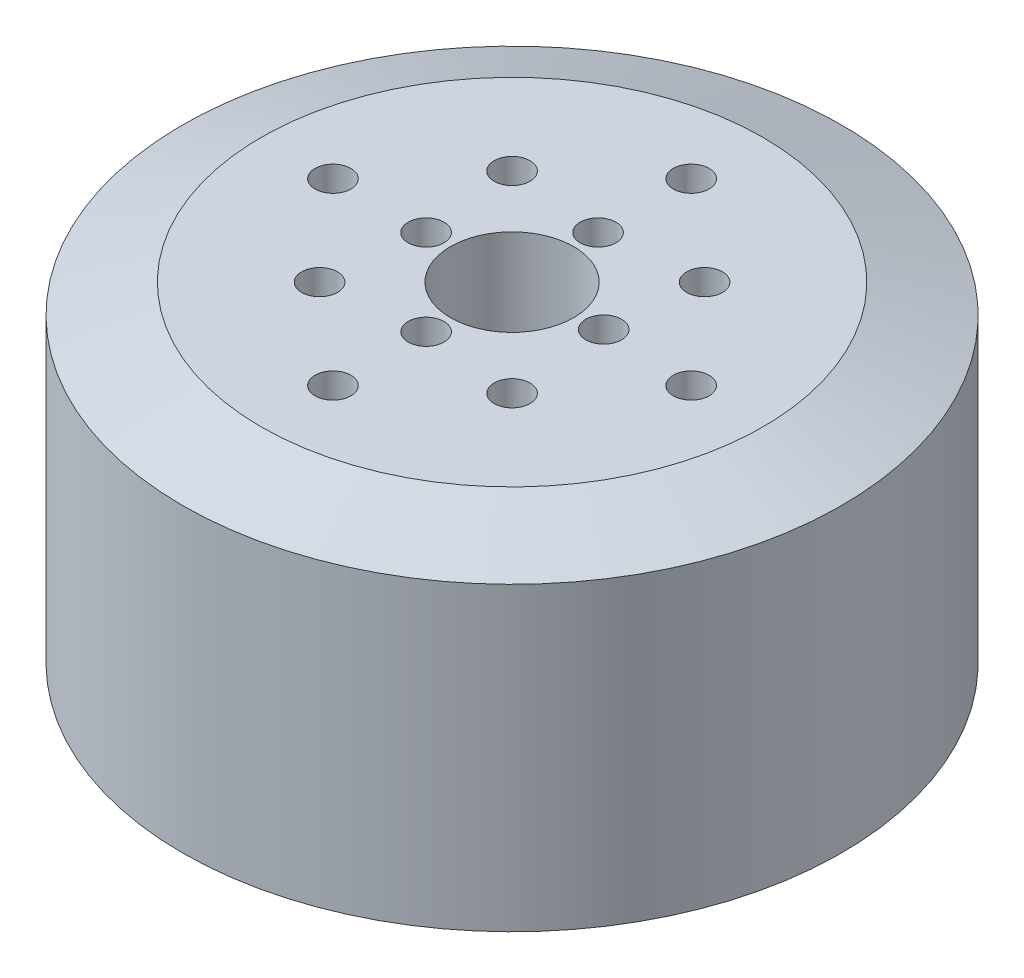
SolidWorks part; units mm, degrees
material "3.1355 (EN-AW 2024)"
ref_plane "Спереди" through (0, 0, 0) normal (0, 0, 1) x (1, 0, 0)
ref_plane "Сверху" through (0, 0, 0) normal (0, 1, 0) x (1, 0, 0)
ref_plane "Справа" through (0, 0, 0) normal (1, 0, 0) x (0, 0, -1)
sketch "Эскиз1" plane through (0, 0, 0) normal (0, 1, 0) x (1, 0, 0)
  circle A0 centre (0, 0) radius 23
  dimension "D1" = 46
extrude "Бобышка-Вытянуть1" add sketch "Эскиз1" along normal blind 23
chamfer "Фаска1" distance 2 angle 70 1 edges at (0, 23, 23) first distance on face at (0, 23, 23)
sketch "Эскиз2" plane through (0, 23, 0) normal (0, 1, 0) x (1, 0, 0)
  circle A0 centre (0, 0) radius 3.5
  circle A1 centre (0, 0) radius 5
  dimension "D1" = 7
  dimension "D2" = 10
extrude "Вырез-Вытянуть1" cut sketch "Эскиз2" against normal through all contours A0 region at (0, 23, 0)
extrude "Бобышка-Вытянуть2" add sketch "Эскиз2<3>" against normal blind 32
sketch "Эскиз2<3>" plane through (0, 23, 0) normal (0, 1, 0) x (1, 0, 0) same geometry as "Эскиз2"
sketch "Эскиз3" plane through (0, 23, 0) normal (0, 1, 0) x (1, 0, 0)
  line L0 (9.5, 0) -> (0, 0) construction
  line L1 (0, 0) -> (6.7175, 6.7175) construction
  line L2 (0, 0) -> (6.7175, -6.7175) construction
  line L3 (0, 0) -> (-6.7175, -6.7175) construction
  line L4 (0, 0) -> (-6.7175, 6.7175) construction
  circle A0 centre (0, 0) radius 6 construction
  circle A1 centre (0, 0) radius 12.5 construction
  circle A2 centre (0, 0) radius 9.5 construction
  point P4 (0, 12.5)
  point P5 (0, -12.5)
  point P6 (-12.5, 0)
  point P7 (12.5, 0)
  point P8 (6, 0)
  point P9 (0, 6)
  point P10 (-6, 0)
  point P11 (0, -6)
  point P21 (0, 0)
  dimension "D1" = 12
  dimension "D2" = 25
  dimension "D3" = 19
  dimension "D4" = 45
  dimension "D5" = 4
sketch "Эскиз4" plane through (0, 0, 0) normal (0, -1, 0) x (1, 0, 0)
  circle A1 centre (0, 0) radius 5 construction
  circle A2 centre (0, 0) radius 21
  circle A3 centre (0, 0) radius 21
  circle A4 centre (0, 0) radius 5
  dimension "D1" = 2
extrude "Вырез-Вытянуть2" cut sketch "Эскиз4" against normal blind 19
hole_wizard "Отверстие обработанное метчиком M3x0.51" positions "Эскиз6" profile "Эскиз5" tap size "M3x0.5" standard "Ansi Metric" end condition through all
sketch "Эскиз6" plane through (0, 23, 0) normal (0, 1, 0) x (1, 0, 0)
  point P0 (0, 12.5)
  point P3 (12.5, 0)
  point P6 (0, -12.5)
  point P9 (-12.5, 0)
sketch "Эскиз5" plane through (0, 23, -12.5) normal (1, 0, 0) x (0, 0, 1)
  line L0 (0, 0) -> (0, 32)
  line L1 (0, 32) -> (1.25, 32)
  line L2 (1.25, 32) -> (1.25, 0)
  line L5 (1.25, 0) -> (0, 0)
  line L11 (0, -6.35) -> (0, 107.95) construction
  dimension "Диаметр проходного сверла" = 2.5
  dimension "Глубина проходного сверла" = 32
cosmetic thread "Отверстие резьбы1" parameters "D2"=3
cosmetic thread "Отверстие резьбы2" parameters "D2"=3
cosmetic thread "Отверстие резьбы3" parameters "D2"=3
cosmetic thread "Отверстие резьбы4" parameters "D2"=3
hole_wizard "Отверстие обработанное метчиком M3x0.52" positions "Эскиз8" profile "Эскиз7" tap size "M3x0.5" standard "Ansi Metric"
sketch "Эскиз8" plane through (0, 23, 0) normal (0, 1, 0) x (1, 0, 0)
  point P0 (6.0622, 0.332)
  point P2 (0, 6)
  point P5 (-6, 0)
  point P8 (0, -6)
cosmetic thread "Отверстие резьбы5" parameters "D1"=6, "D2"=3
cosmetic thread "Отверстие резьбы6" parameters "D1"=6, "D2"=3
cosmetic thread "Отверстие резьбы7" parameters "D1"=6, "D2"=3
cosmetic thread "Отверстие резьбы8" parameters "D1"=6, "D2"=3
sketch "Эскиз7" plane through (6.0622, 23, -0.332) normal (1, 0, 0) x (0, 0, 1)
  line L0 (0, 0) -> (0, 8.2511)
  line L1 (0, 8.2511) -> (1.25, 7.5)
  line L2 (1.25, 7.5) -> (1.25, 0)
  line L5 (1.25, 0) -> (0, 0)
  line L10 (0, 8.2511) -> (-1.25, 7.5) construction
  line L11 (0, -6.35) -> (0, 107.95) construction
  dimension "Диаметр сверла" = 2.5
  dimension "Глубина сверла" = 7.5
  dimension "Угол заточки сверла" = 118
sketch "Эскиз9" plane through (0, 23, 0) normal (0, 1, 0) x (1, 0, 0)
  point P3 (0, -6)
  point P5 (6.0622, 0.332)
hole_wizard "Отверстие обработанное метчиком M3x0.53" positions "Эскиз11" profile "Эскиз10" tap size "M3x0.5" standard "Ansi Metric" end condition through all
sketch "Эскиз11" plane through (0, 23, 0) normal (0, 1, 0) x (1, 0, 0)
  point P0 (-6.7175, 6.7175)
  point P3 (6.7175, 6.7175)
  point P6 (6.7175, -6.7175)
  point P9 (-6.7175, -6.7175)
cosmetic thread "Отверстие резьбы9" parameters "D2"=3
cosmetic thread "Отверстие резьбы10" parameters "D2"=3
cosmetic thread "Отверстие резьбы11" parameters "D2"=3
cosmetic thread "Отверстие резьбы12" parameters "D2"=3
sketch "Эскиз10" plane through (-6.7175, 23, -6.7175) normal (1, 0, 0) x (0, 0, 1)
  line L0 (0, 0) -> (0, 32)
  line L1 (0, 32) -> (1.25, 32)
  line L2 (1.25, 32) -> (1.25, 0)
  line L5 (1.25, 0) -> (0, 0)
  line L11 (0, -6.35) -> (0, 107.95) construction
  dimension "Диаметр проходного сверла" = 2.5
  dimension "Глубина проходного сверла" = 32
sketch "Эскиз12" plane through (0, 23, 0) normal (0, 1, 0) x (1, 0, 0)
  circle A0 centre (0, 0) radius 4.3
  dimension "D1" = 8.6
extrude "Вырез-Вытянуть3" cut sketch "Эскиз12" against normal blind 25
sketch "Эскиз13" plane through (0, 23, 0) normal (0, 1, 0) x (1, 0, 0)
  line L1 (-7.2175, 7.2175) -> (-6.2175, 7.2175)
  line L2 (-7.2175, 7.2175) -> (-7.2175, 6.2175)
  line L3 (-7.2175, 6.2175) -> (-6.2175, 6.2175)
  line L4 (-6.2175, 7.2175) -> (-6.2175, 6.2175)
  line L5 (-7.2175, 7.2175) -> (-6.2175, 6.2175) construction
  line L6 (-7.2175, 6.2175) -> (-6.2175, 7.2175) construction
  point P0 (-6.7175, 6.7175)
  point P1 (6.7175, 6.7175)
  point P3 (6.7175, -6.7175)
  point P5 (-6.7175, 6.7175)
  dimension "D1" = 1
equation "\"D2@Эскиз2\"=\"D1@Эскиз2\"+3"
